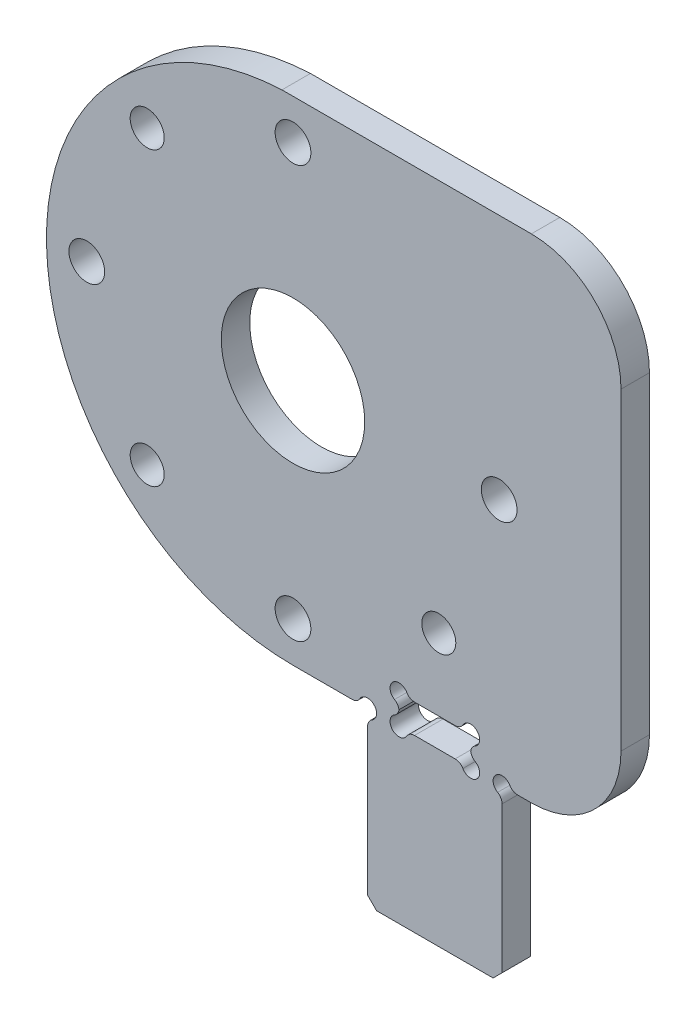
SolidWorks part; units mm, degrees
material "Balsa"
ref_plane "Front Plane" through (0, 0, 0) normal (0, 0, 1) x (1, 0, 0)
ref_plane "Top Plane" through (0, 0, 0) normal (0, 1, 0) x (1, 0, 0)
ref_plane "Right Plane" through (0, 0, 0) normal (1, 0, 0) x (0, 0, -1)
sketch "Sketch1" plane through (0, 0, 0) normal (0, 0, 1) x (1, 0, 0)
  line L0 (-56.9454, 94.4454) -> (-37.5, 75) construction
  line L1 (-40.4988, 0) -> (0, 0)
  line L2 (-75, 55) -> (-75, 75)
  line L3 (-40.4988, 0) -> (-83.323, 0)
  line L4 (0, 0) -> (0, 75)
  line L5 (-37.5, 75) -> (-65, 75) construction
  line L6 (-75, 75) -> (0, 0) construction
  line L7 (-18.0546, 94.4454) -> (-37.5, 75) construction
  line L8 (-75, 55) -> (-83.323, 55)
  line L9 (-37.5, 75) -> (-18.0546, 55.5546) construction
  line L10 (-83.323, 27.5) -> (-83.323, 50.5) construction
  arc A0 (-75, 75) -> (0, 75) centre (-37.5, 75) cw
  arc A1 (-83.323, 55) -> (-83.323, 0) centre (-83.323, 27.5) ccw
  circle A2 centre (-83.323, 27.5) radius 8
  circle A3 centre (-37.5, 75) radius 10 construction
  circle A4 centre (-83.323, 27.5) radius 23 construction
  circle A5 centre (-67.0596, 11.2365) radius 1.8987
  circle A6 centre (-83.323, 50.5) radius 1.9939
  circle A7 centre (-99.5865, 11.2365) radius 1.8987
  circle A8 centre (-60.323, 27.5) radius 1.9939
  circle A9 centre (-99.5865, 43.7635) radius 1.8987
  circle A10 centre (-83.323, 4.5) radius 1.9939
  circle A11 centre (-106.323, 27.5) radius 1.9939
  circle A13 centre (-37.5, 75) radius 27.5 construction
  circle A14 centre (-37.5, 102.5) radius 1.75 construction
  circle A15 centre (-65, 75) radius 1.75 construction
  circle A16 centre (-10, 75) radius 1.75 construction
  circle A17 centre (-37.5, 47.5) radius 1.75 construction
  circle A18 centre (-56.9454, 94.4454) radius 1.5 construction
  circle A19 centre (-18.0546, 94.4454) radius 1.5 construction
  circle A20 centre (-18.0546, 55.5546) radius 1.5 construction
  circle A21 centre (-56.9454, 55.5546) radius 1.5 construction
  circle A22 centre (-37.5, 75) radius 13 construction
  circle A23 centre (-37.5, 88) radius 1.8 construction
  circle A24 centre (-24.5, 75) radius 1.8 construction
  circle A25 centre (-37.5, 62) radius 1.8 construction
  circle A26 centre (-50.5, 75) radius 1.8 construction
  circle A28 centre (-67.0596, 43.7635) radius 1.8987 [skipped]
  point P0 (0, 0)
  point P63 (-83.323, 27.5)
  dimension "D3" = 27.5
  dimension "D5" = 20
  dimension "D6" = 16
  dimension "D7" = 46
  dimension "D9" = 3.7973
  dimension "D10" = 4
  dimension "D12" = 55
  dimension "D13" = 3
  dimension "D16" = 3
  dimension "D17" = 3.6
  dimension "D18" = 3.5
  dimension "D8" = 3.9878
  dimension "D1" = 75
  dimension "D2" = 66
  dimension "D4" = 75
  dimension "D14" = 45
  dimension "D11" = 4
  dimension "D15" = 4
extrude "Boss-Extrude1" add sketch "Sketch1" along normal blind 3.175
fillet "Fillet1" radius 10 1 edges at (-75, 55, 1.5875)
sketch "Sketch2" plane through (0, 0, 0) normal (0, 0, -1) x (-1, 0, 0)
  line L0 (83.323, 0) -> (0, 0) construction
  line L1 (0, 0) -> (15, 0)
  line L2 (0, 0) -> (0, -19.05)
  line L3 (0, -19.05) -> (15, -19.05)
  line L4 (15, 0) -> (15, -19.05)
  line L5 (30, 0) -> (45, 0)
  line L6 (30, 0) -> (30, -19.05)
  line L7 (30, -19.05) -> (45, -19.05)
  line L8 (45, 0) -> (45, -19.05)
  line L10 (60, 0) -> (75, 0)
  line L11 (60, 0) -> (60, -19.05)
  line L12 (60, -19.05) -> (75, -19.05)
  line L13 (75, 0) -> (75, -19.05)
  dimension "D1" = 15
  dimension "D2" = 15
  dimension "D3" = 19.05
  dimension "D4" = 15
extrude "Boss-Extrude2" add sketch "Sketch2" against normal up to surface (3.175 mm away) up to face at (-57.125, 50.8196, 3.175)
sketch "Sketch3" plane through (0, 0, 3.175) normal (0, 0, 1) x (1, 0, 0)
  circle A0 centre (-75, 0) radius 1
  circle A1 centre (-60, 0) radius 1
  circle A2 centre (-45, 0) radius 1
  circle A3 centre (-30, 0) radius 1
  circle A4 centre (-15, 0) radius 1
  dimension "D1" = 2
extrude "Cut-Extrude1" cut sketch "Sketch3" against normal through all
chamfer "Chamfer1" distance 1 angle 45 6 edges at (0, -19.05, 1.5875) (-15, -19.05, 1.5875) (-30, -19.05, 1.5875) (-45, -19.05, 1.5875) (-60, -19.05, 1.5875) (-75, -19.05, 1.5875)
other "Move Face1" [suppressed] offset 0.08 parameters "D1"=0.08
fillet "Fillet2" radius 1 10 edges at (-30, -1, 1.5875) (-29, 0, 1.5875) (-16, 0, 1.5875) (-15, -1, 1.5875) (-46, 0, 1.5875) (-45, -1, 1.5875) (-60, -1, 1.5875) (-59, 0, 1.5875) (-76, 0, 1.5875) (-75, -1, 1.5875)
sketch "Sketch4" plane through (0, 0, 3.175) normal (0, 0, 1) x (1, 0, 0)
  line L1 (-71.4967, 0) -> (-63.5033, 0)
  line L2 (-71.4967, 0) -> (-71.4967, 3.2207)
  line L3 (-71.4967, 3.2207) -> (-63.5033, 3.2207)
  line L4 (-63.5033, 0) -> (-63.5033, 3.2207)
  line L5 (-67.5, -19.05) -> (-67.5, 16.6012) construction
  line L8 (-61, -19.05) -> (-74, -19.05) construction
  point P9 (-67.5, 0)
  dimension "D1" = 3.2207
  dimension "D2" = 7.9934
extrude "Cut-Extrude2" cut sketch "Sketch4" against normal through all
sketch "Sketch5" plane through (0, 0, 0) normal (0, 0, -1) x (-1, 0, 0)
  line L0 (84.5528, 54.9725) -> (46.7321, 54.9725)
  line L1 (46.7321, 54.9725) -> (46.7321, 0)
  line L2 (84.5528, 54.9725) -> (84.5528, 112.5)
  line L3 (84.5528, 112.5) -> (0, 112.5)
  line L4 (0, 112.5) -> (0, -19.05)
  line L5 (0, -19.05) -> (46.7321, -19.05)
  line L6 (46.7321, -19.05) -> (46.7321, 0)
  line L7 (31, -19.05) -> (44, -19.05) construction
  line L8 (0, -18.05) -> (0, 75) construction
  arc A0 (75, 75) -> (0, 75) centre (37.5, 75) ccw construction
extrude "Cut-Extrude3" cut sketch "Sketch5" against normal through all
fillet "Fillet3" radius 10 2 edges at (-46.7321, 54.9725, 1.5875) (-46.7321, 0, 1.5875)
sketch "Sketch6" plane through (0, 0, 0) normal (0, 0, -1) x (-1, 0, 0)
  circle A0 centre (63.5033, 3.2207) radius 1
  circle A1 centre (71.4967, 3.2207) radius 1
  circle A2 centre (71.4967, 0) radius 1
  circle A3 centre (63.5033, 0) radius 1
  dimension "D1" = 2
extrude "Cut-Extrude4" cut sketch "Sketch6" against normal through all
fillet "Fillet4" radius 1 8 edges at (-70.4967, 3.2207, 1.5875) (-71.4967, 2.2207, 1.5875) (-71.4967, 1, 1.5875) (-70.4967, 0, 1.5875) (-64.5033, 0, 1.5875) (-63.5033, 1, 1.5875) (-63.5033, 2.2207, 1.5875) (-64.5033, 3.2207, 1.5875)
